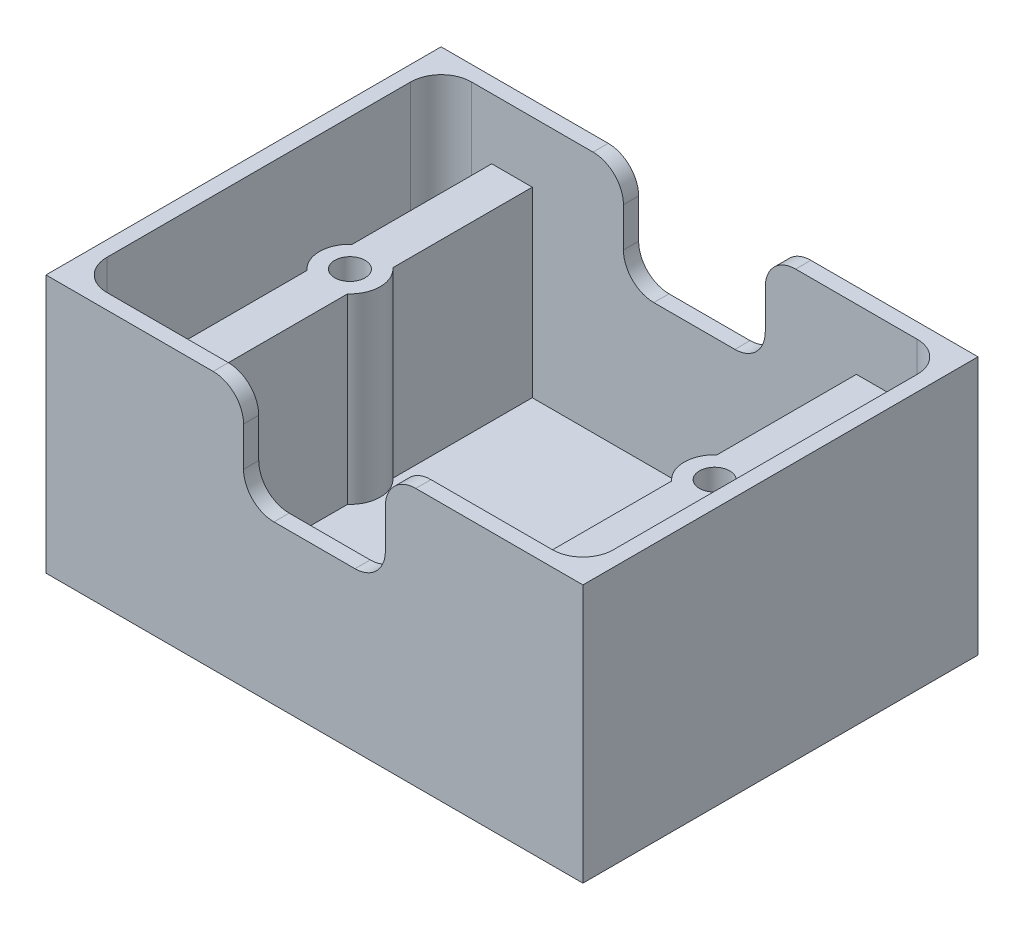
SolidWorks part; units mm, degrees
ref_plane "Front Plane" through (0, 0, 0) normal (0, 0, 1) x (1, 0, 0)
ref_plane "Top Plane" through (0, 0, 0) normal (0, 1, 0) x (1, 0, 0)
ref_plane "Right Plane" through (0, 0, 0) normal (1, 0, 0) x (0, 0, -1)
sketch "Sketch1" plane through (0, 0, 0) normal (0, 1, 0) x (1, 0, 0)
  line L1 (0, 0) -> (50, 0)
  line L2 (0, 0) -> (0, -36)
  line L3 (0, -36) -> (50, -36)
  line L4 (50, 0) -> (50, -36)
  dimension "D1" = 50
  dimension "D2" = 36
extrude "Boss-Extrude1" add sketch "Sketch1" along normal blind 24
shell "Shell1" thickness 1.5 removed face at (25, 24, 18) outward yes
sketch "Sketch2" plane through (0, 0, 0) normal (0, 1, 0) x (1, 0, 0)
  line L0 (50, 0) -> (0, 0) construction
  line L1 (5, 0) -> (9, 0)
  line L2 (5, 0) -> (5, -36)
  line L3 (5, -36) -> (9, -36)
  line L4 (9, 0) -> (9, -36)
  line L5 (0, -36) -> (50, -36) construction
  line L6 (25, 0) -> (25, -71.172) construction
  line L7 (45, -36) -> (41, -36)
  line L8 (41, 0) -> (41, -36)
  line L9 (45, 0) -> (41, 0)
  line L10 (45, 0) -> (45, -36)
  dimension "D1" = 4
  dimension "D2" = 16
extrude "Boss-Extrude2" add sketch "Sketch2" along normal blind 18
sketch "Sketch3" plane through (0, 0, 0) normal (0, 1, 0) x (1, 0, 0)
  line L0 (-7.5821, -25) -> (66.7821, -25) construction
sketch "Sketch4" plane through (0, 18, 0) normal (0, 1, 0) x (1, 0, 0)
  line L0 (25, -36) -> (25, -57.4435) construction
  line L2 (0, -36) -> (50, -36) construction
  circle A0 centre (7, -16) radius 3
  circle A2 centre (43, -16) radius 3
  dimension "D1" = 6
  dimension "D2" = 18
  dimension "D3" = 20
sketch "Sketch6" plane through (0, 0, 37.5) normal (0, 0, 1) x (1, 0, 0)
  line L0 (25, 24) -> (25, -9.6606) construction
  line L1 (18, 14.1347) -> (32, 14.1347)
  line L2 (18, 14.1347) -> (18, 28.1347)
  line L3 (18, 28.1347) -> (32, 28.1347)
  line L4 (32, 14.1347) -> (32, 28.1347)
  line L5 (-1.5, 24) -> (51.5, 24) construction
  dimension "D1" = 14
  dimension "D2" = 7
  dimension "D3" = 14
extrude "Cut-Extrude2" cut sketch "Sketch6" against normal blind 58
fillet "Fillet1" radius 3 12 edges at (50, 12, 36) (0, 12, 36) (50, 12, 0) (0, 12, 0) (18, 24, -0.75) (18, 14.1347, -0.75) (32, 14.1347, -0.75) (32, 24, -0.75) (18, 24, 36.75) (18, 14.1347, 36.75) (32, 14.1347, 36.75) (32, 24, 36.75)
extrude "Boss-Extrude3" add sketch "Sketch4" against normal up to surface (18 mm away) up to face at (25, 0, 18)
sketch "Sketch7" plane through (0, 18, 0) normal (0, 1, 0) x (1, 0, 0)
  line L0 (25, -36) -> (25, -57.6999) construction
  line L1 (29, -36) -> (21, -36) construction
  line L2 (5, -36) -> (9, -36) construction
  circle A0 centre (7, -16) radius 1.5
  circle A1 centre (43, -16) radius 1.5
  dimension "D1" = 18
  dimension "D2" = 20
extrude "Cut-Extrude3" cut sketch "Sketch7" against normal blind 10
